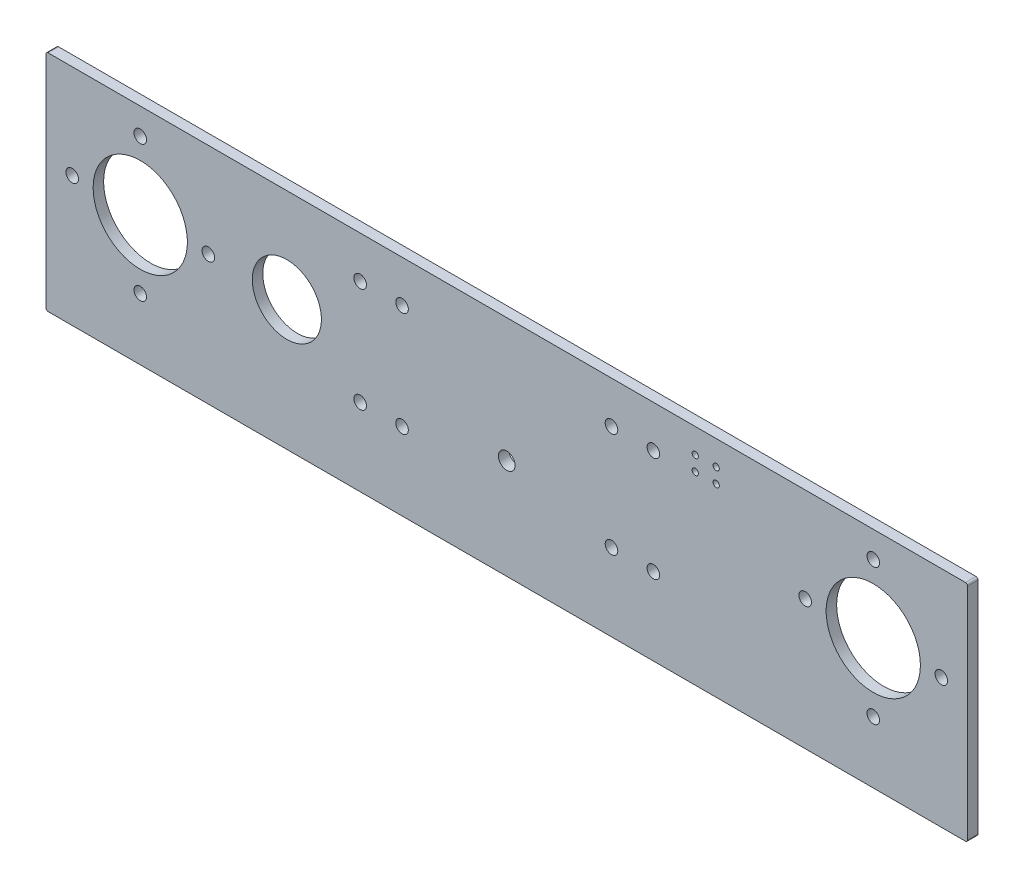
SolidWorks part; units mm, degrees
ref_plane "前视基准面" through (0, 0, 0) normal (0, 0, 1) x (1, 0, 0)
ref_plane "上视基准面" through (0, 0, 0) normal (0, 1, 0) x (1, 0, 0)
ref_plane "右视基准面" through (0, 0, 0) normal (1, 0, 0) x (0, 0, -1)
sketch "草图1" plane through (0, 0, 0) normal (0, 0, 1) x (1, 0, 0)
  line L1 (-220, -53.5) -> (220, -53.5)
  line L2 (-220, -53.5) -> (-220, 53.5)
  line L3 (-220, 53.5) -> (220, 53.5)
  line L4 (220, -53.5) -> (220, 53.5)
  line L5 (-220, -53.5) -> (220, 53.5) construction
  line L6 (-220, 53.5) -> (220, -53.5) construction
  point P0 (0, 0)
  dimension "D1" = 107
  dimension "D2" = 440
base flange "基体-法兰1" sketch "草图1" thickness 5 reverse thickness direction no parameters "D1"=10
sketch "草图8" plane through (0, 0, 0) normal (0, 0, 1) x (1, 0, 0)
  line L0 (220, -53.5) -> (220, 53.5) construction
  line L1 (-220, -53.5) -> (220, -53.5) construction
  circle A0 centre (175, 8.5) radius 22.5
  dimension "D3" = 45
  dimension "D1" = 45
  dimension "D2" = 62
extrude "切除-拉伸1" cut sketch "草图8" against normal blind 10 normal cut yes
sketch "草图9" plane through (0, 0, 0) normal (0, 0, 1) x (1, 0, 0)
  circle A0 centre (175, 41) radius 3
  circle A1 centre (175, 8.5) radius 22.5 construction
  circle A2 centre (207.5, 8.5) radius 3
  circle A3 centre (175, -24) radius 3
  circle A4 centre (142.5, 8.5) radius 3
  point P13 (175, 8.5)
  dimension "D1" = 6
  dimension "D2" = 32.5
  dimension "D3" = 4
extrude "切除-拉伸2" cut sketch "草图9" against normal blind 10 normal cut yes
mirror "镜向1" about plane through (0, 0, 0) normal (1, 0, 0) of "切除-拉伸1", "切除-拉伸2"
sketch "草图10" plane through (0, 0, -5) normal (0, 0, -1) x (-1, 0, 0)
  line L0 (220, 53.5) -> (220, -53.5) construction
  line L1 (220, -53.5) -> (-220, -53.5) construction
  circle A0 centre (105, 8.5) radius 16.5
  dimension "D3" = 33
  dimension "D1" = 115
  dimension "D2" = 62
extrude "切除-拉伸3" cut sketch "草图10" against normal blind 10 normal cut yes
sketch "草图11" plane through (0, 0, -5) normal (0, 0, -1) x (-1, 0, 0)
  circle A0 centre (0, -5.6305) radius 4
  dimension "D1" = 8
extrude "切除-拉伸4" cut sketch "草图11" against normal blind 10 normal cut yes
ref_plane "基准面4" through (0, 8.5, 0) normal (0, 1, 0) x (1, 0, 0)
sketch "草图12" plane through (0, 0, -5) normal (0, 0, -1) x (-1, 0, 0)
  line L0 (-220, 53.5) -> (220, 53.5) construction
  circle A0 centre (-70, 33.5) radius 3
  circle A1 centre (-50, 33.5) radius 3
  dimension "D1" = 6
  dimension "D2" = 6
  dimension "D3" = 20
  dimension "D4" = 20
  dimension "D5" = 20
  dimension "D6" = 50
extrude "切除-拉伸5" cut sketch "草图12" against normal blind 10 normal cut yes
mirror "镜向2" about plane through (0, 0, 0) normal (1, 0, 0) of "切除-拉伸5"
mirror "镜向3" about plane through (0, 8.5, 0) normal (0, 1, 0) of "镜向2", "切除-拉伸5"
fillet "圆角1" radius 1 4 edges at (-220, -53.5, -2.5) (-220, 53.5, -2.5) (220, -53.5, -2.5) (220, 53.5, -2.5)
sketch "草图13" plane through (0, 0, -5) normal (0, 0, -1) x (-1, 0, 0)
  line L0 (-219, 53.5) -> (219, 53.5) construction
  line L1 (-220, -52.5) -> (-220, 52.5) construction
  circle A0 centre (-100, 41.75) radius 1.5
  circle A1 centre (-90, 41.75) radius 1.5
  circle A2 centre (-90, 34.75) radius 1.5
  circle A3 centre (-100, 34.75) radius 1.5
  dimension "D1" = 3
  dimension "D2" = 3
  dimension "D3" = 3
  dimension "D4" = 3
  dimension "D5" = 7
  dimension "D6" = 7
  dimension "D7" = 11.75
  dimension "D8" = 11.75
  dimension "D9" = 10
  dimension "D10" = 120
  dimension "D11" = 10
extrude "切除-拉伸6" cut sketch "草图13" against normal blind 10 normal cut yes
sketch "折弯-线1" [suppressed] plane through (0, 0, 0) normal (0, 1, 0) x (1, 0, 0)
sketch "边界框1" [suppressed] plane through (0, 0, 0) normal (0, 1, 0) x (1, 0, 0)
sheet metal parameters "钣金3" thickness 5 parameters "D1"=10
flat pattern "平板型式3" [suppressed]
sketch "折弯-线3" plane through (0, 0, 0) normal (0, 1, 0) x (1, 0, 0)
sketch3d "边界框3" [suppressed]
  line L0 (230, -53.5, 0) -> (-230, -53.5, 0) construction
  line L1 (230, 53.5, 0) -> (-230, 53.5, 0) construction
  line L2 (230, -53.5, 0) -> (230, 53.5, 0) construction
  line L3 (-230, -53.5, 0) -> (-230, 53.5, 0) construction
sheet metal parameters "钣金4" thickness 5 parameters "D1"=10
flat pattern "平板型式3"
sketch "折弯-线3" plane through (0, 0, 0) normal (0, 1, 0) x (1, 0, 0)
sketch3d "边界框3" [suppressed]
  line L0 (-230, -53.5, 0) -> (230, -53.5, 0) construction
  line L1 (-230, 53.5, 0) -> (230, 53.5, 0) construction
  line L2 (-230, -53.5, 0) -> (-230, 53.5, 0) construction
  line L3 (230, -53.5, 0) -> (230, 53.5, 0) construction
sheet metal parameters "钣金5" thickness 5 parameters "D1"=10
flat pattern "平板型式3"
sketch "折弯-线3" plane through (0, 0, 0) normal (0, 1, 0) x (1, 0, 0)
sketch3d "边界框3" [suppressed]
  line L0 (-230, -53.5, 0) -> (230, -53.5, 0) construction
  line L1 (-230, 53.5, 0) -> (230, 53.5, 0) construction
  line L2 (-230, -53.5, 0) -> (-230, 53.5, 0) construction
  line L3 (230, -53.5, 0) -> (230, 53.5, 0) construction
sheet metal parameters "钣金6" thickness 5 parameters "D1"=10
flat pattern "平板型式3"
sketch "折弯-线3" plane through (0, 0, 0) normal (0, 1, 0) x (1, 0, 0)
sketch3d "边界框3" [suppressed]
  line L0 (-230, -53.5, 0) -> (230, -53.5, 0) construction
  line L1 (-230, 53.5, 0) -> (230, 53.5, 0) construction
  line L2 (-230, -53.5, 0) -> (-230, 53.5, 0) construction
  line L3 (230, -53.5, 0) -> (230, 53.5, 0) construction
sheet metal parameters "钣金7" thickness 5 parameters "D1"=10
flat pattern "平板型式3"
sketch "折弯-线3" plane through (0, 0, 0) normal (0, 1, 0) x (1, 0, 0)
sketch3d "边界框3" [suppressed]
  line L0 (-220, -53.5, 0) -> (220, -53.5, 0) construction
  line L1 (-220, 53.5, 0) -> (220, 53.5, 0) construction
  line L2 (-220, -53.5, 0) -> (-220, 53.5, 0) construction
  line L3 (220, -53.5, 0) -> (220, 53.5, 0) construction
sheet metal parameters "钣金8" thickness 5 parameters "D1"=10
flat pattern "平板型式3"
sketch "折弯-线3" plane through (0, 0, 0) normal (0, 1, 0) x (1, 0, 0)
sketch3d "边界框3" [suppressed]
  line L0 (-220, -53.5, 0) -> (220, -53.5, 0) construction
  line L1 (-220, 53.5, 0) -> (220, 53.5, 0) construction
  line L2 (-220, -53.5, 0) -> (-220, 53.5, 0) construction
  line L3 (220, -53.5, 0) -> (220, 53.5, 0) construction
sheet metal parameters "钣金9" thickness 5 parameters "D1"=10
flat pattern "平板型式3"
sketch "折弯-线3" plane through (0, 0, 0) normal (0, 1, 0) x (1, 0, 0)
sketch3d "边界框3" [suppressed]
  line L0 (-220, -53.5, 0) -> (220, -53.5, 0) construction
  line L1 (-220, 53.5, 0) -> (220, 53.5, 0) construction
  line L2 (-220, -53.5, 0) -> (-220, 53.5, 0) construction
  line L3 (220, -53.5, 0) -> (220, 53.5, 0) construction
sheet metal parameters "钣金10" thickness 5 parameters "D1"=10
flat pattern "平板型式3"
sketch "折弯-线3" plane through (0, 0, 0) normal (0, 1, 0) x (1, 0, 0)
sketch3d "边界框3" [suppressed]
  line L0 (-220, -53.5, 0) -> (220, -53.5, 0) construction
  line L1 (-220, 53.5, 0) -> (220, 53.5, 0) construction
  line L2 (-220, -53.5, 0) -> (-220, 53.5, 0) construction
  line L3 (220, -53.5, 0) -> (220, 53.5, 0) construction
sheet metal parameters "钣金11" thickness 5 parameters "D1"=10
flat pattern "平板型式3"
sketch "折弯-线3" plane through (0, 0, 0) normal (0, 1, 0) x (1, 0, 0)
sketch3d "边界框3" [suppressed]
  line L0 (-220, -53.5, 0) -> (220, -53.5, 0) construction
  line L1 (-220, 53.5, 0) -> (220, 53.5, 0) construction
  line L2 (-220, -53.5, 0) -> (-220, 53.5, 0) construction
  line L3 (220, -53.5, 0) -> (220, 53.5, 0) construction
sheet metal parameters "钣金12" thickness 5 parameters "D1"=10
flat pattern "平板型式3"
sketch "折弯-线3" plane through (0, 0, 0) normal (0, 1, 0) x (1, 0, 0)
sketch3d "边界框3" [suppressed]
  line L0 (-220, -53.5, 0) -> (220, -53.5, 0) construction
  line L1 (-220, 53.5, 0) -> (220, 53.5, 0) construction
  line L2 (-220, -53.5, 0) -> (-220, 53.5, 0) construction
  line L3 (220, -53.5, 0) -> (220, 53.5, 0) construction
